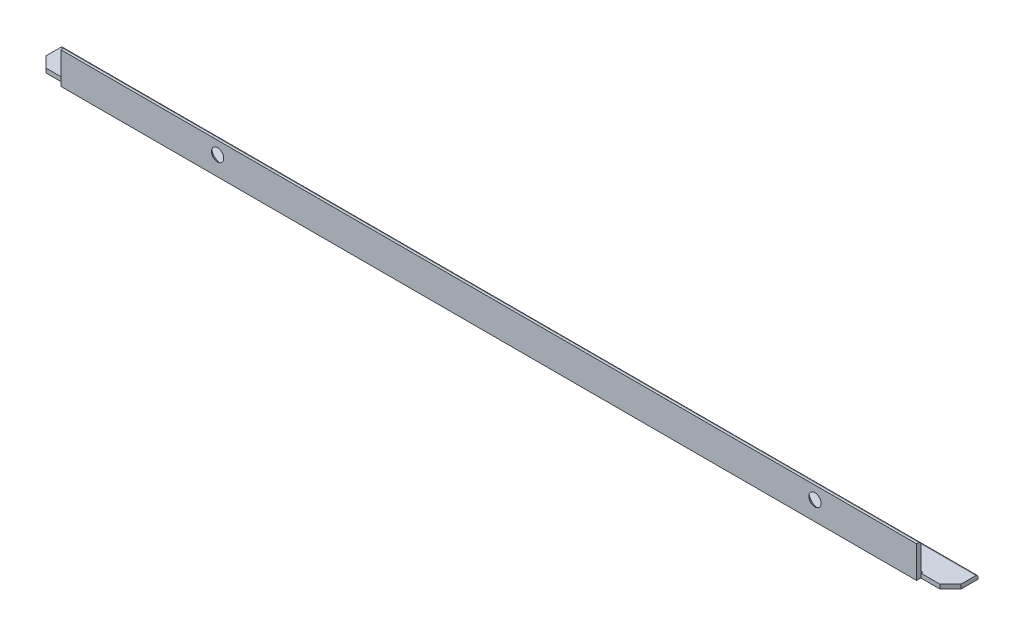
SolidWorks part; units mm, degrees
material "1060 Сплав"
ref_plane "Front" through (0, 0, 0) normal (0, 0, 1) x (1, 0, 0)
ref_plane "Top" through (0, 0, 0) normal (0, 1, 0) x (1, 0, 0)
ref_plane "Right" through (0, 0, 0) normal (1, 0, 0) x (0, 0, -1)
sketch "Эскиз1" plane through (0, 0, 0) normal (1, 0, 0) x (0, 0, -1)
  line L0 (0, 0) -> (0, 15)
  line L1 (0, 0) -> (15, 0)
  line L2 (0, 15) -> (1, 15)
  line L3 (2, 14) -> (2, 3)
  line L4 (3, 2) -> (14, 2)
  line L5 (15, 1) -> (15, 0)
  arc A0 (14, 2) -> (15, 1) centre (14, 1) cw
  arc A1 (1, 15) -> (2, 14) centre (1, 14) cw
  arc A2 (2, 3) -> (3, 2) centre (3, 3) ccw
  point P9 (15, 2)
  point P12 (2, 15)
  dimension "D5" = 1
  dimension "D1" = 15
  dimension "D2" = 15
  dimension "D3" = 2
  dimension "D4" = 2
extrude "Бобышка-Вытянуть1" add sketch "Эскиз1" along normal blind 432
sketch "Эскиз6" plane through (432, 0, 0) normal (1, 0, 0) x (0, 0, -1)
  line L0 (0, 0) -> (15, 0) construction
  line L1 (0, 15) -> (2, 15)
  line L2 (0, 15) -> (0, 0)
  line L3 (0, 0) -> (2, 0)
  line L4 (2, 0) -> (2, 2)
  line L5 (2, 2) -> (3, 2)
  line L6 (3, 2) -> (3, 15)
  line L7 (3, 15) -> (2, 15)
extrude "Вырез-Вытянуть5" cut sketch "Эскиз6" against normal blind 14
sketch "Эскиз7" plane through (0, 0, 0) normal (-1, 0, 0) x (0, 0, 1)
  line L0 (0, 0) -> (-15, 0) construction
  line L1 (0, 15) -> (-2, 15)
  line L2 (0, 15) -> (0, 0)
  line L3 (0, 0) -> (-2, 0)
  line L4 (-3, 2) -> (-2, 2)
  line L5 (-2, 2) -> (-2, 0)
  line L6 (-3, 2) -> (-3, 15)
  line L7 (-3, 15) -> (-2, 15)
extrude "Вырез-Вытянуть6" cut sketch "Эскиз7" against normal blind 14
sketch "Эскиз9" plane through (0, 2, 0) normal (0, 1, 0) x (1, 0, 0)
  line L0 (0, 2) -> (0, 7)
  line L1 (0, 14) -> (0, 2) construction
  line L2 (0, 7) -> (5, 2)
  line L3 (14, 2) -> (0, 2) construction
  line L4 (5, 2) -> (0, 2)
  line L5 (432, 2) -> (432, 7)
  line L6 (432, 14) -> (432, 2) construction
  line L7 (432, 7) -> (427, 2)
  line L8 (418, 2) -> (432, 2) construction
  line L9 (427, 2) -> (432, 2)
  dimension "D1" = 5
  dimension "D2" = 5
  dimension "D3" = 5
  dimension "D4" = 5
extrude "Вырез-Вытянуть7" cut sketch "Эскиз9" against normal through all
sketch "Эскиз10" plane through (0, 2, 0) normal (0, 1, 0) x (1, 0, 0)
  line L0 (432, 15) -> (0, 15) construction
  line L1 (0, 14) -> (0, 7) construction
  line L2 (432, 14) -> (432, 7) construction
  circle A0 centre (40, 8) radius 2.3
  circle A1 centre (392, 8) radius 2.3
  dimension "D1" = 4.6
  dimension "D2" = 7
  dimension "D3" = 40
  dimension "D4" = 4.6
  dimension "D5" = 7
  dimension "D6" = 40
extrude "Вырез-Вытянуть8" cut sketch "Эскиз10" against normal through all
chamfer "Фаска1" distance 2.05 angle 45 2 edges at (40, 2, -5.7) (392, 2, -5.7)
sketch "Эскиз11" plane through (0, 0, -2) normal (0, 0, -1) x (-1, 0, 0)
  line L0 (-418, 15) -> (-14, 15) construction
  line L1 (-418, 3) -> (-418, 14) construction
  circle A0 centre (-370, 9) radius 2.8
  circle A1 centre (-88, 9) radius 2.8
  dimension "D1" = 5.6
  dimension "D2" = 6
  dimension "D3" = 48
  dimension "D5" = 282
  dimension "D4" = 2
extrude "Вырез-Вытянуть9" cut sketch "Эскиз11" against normal through all
chamfer "Фаска2" distance 2.098 angle 45 2 edges at (88, 11.8, -2) (370, 11.8, -2)
